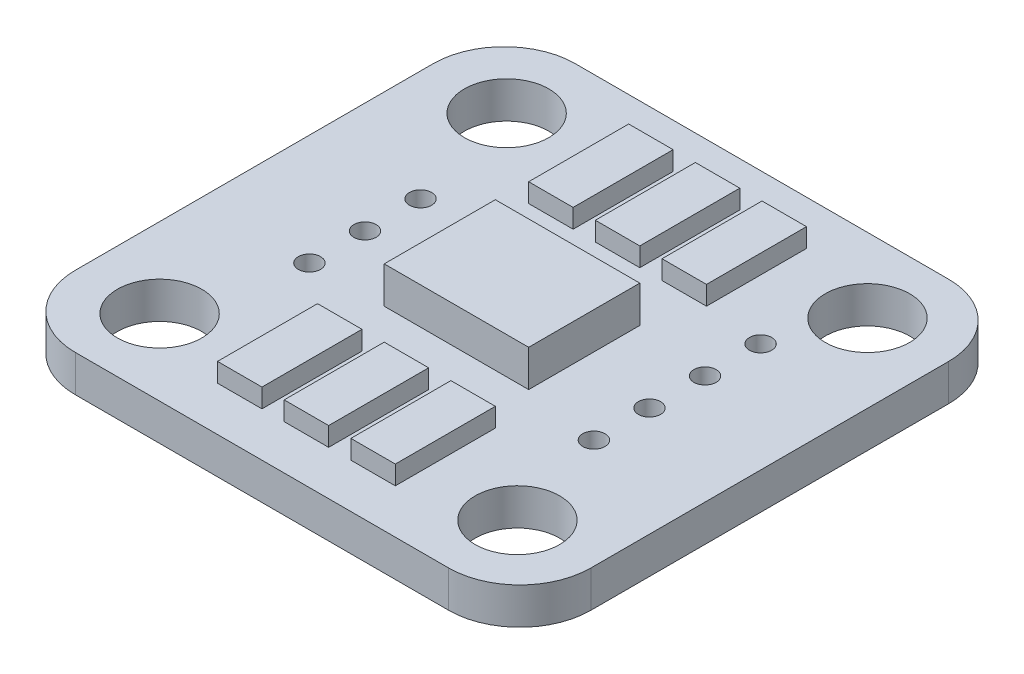
SolidWorks part; units mm, degrees
ref_plane "Front Plane" through (0, 0, 0) normal (0, 0, 1) x (1, 0, 0)
ref_plane "Top Plane" through (0, 0, 0) normal (0, 1, 0) x (1, 0, 0)
ref_plane "Right Plane" through (0, 0, 0) normal (1, 0, 0) x (0, 0, -1)
sketch "Sketch1" plane through (0, 0, 0) normal (0, 1, 0) x (1, 0, 0)
  line L1 (-8.4, -11.25) -> (8.4, -11.25)
  line L2 (-11.6, -8.05) -> (-11.6, 8.05)
  line L3 (-8.4, 11.25) -> (8.4, 11.25)
  line L4 (11.6, -8.05) -> (11.6, 8.05)
  line L5 (-11.6, -11.25) -> (11.6, 11.25) construction
  line L6 (-11.6, 11.25) -> (11.6, -11.25) construction
  line L7 (-8.0152, -7.8409) -> (8.0848, -7.8409) construction
  line L8 (-8.0152, -7.8409) -> (-8.0152, 7.7733) construction
  line L10 (8.0848, -7.8409) -> (8.0848, 7.9091) construction
  line L11 (-8.0152, -7.8409) -> (8.0848, 7.9091) construction
  line L12 (-8.0152, 7.7733) -> (8.0848, -7.8409) construction
  circle A0 centre (-8.0152, 7.7733) radius 1.9
  circle A1 centre (8.0848, 7.9091) radius 1.9
  circle A2 centre (8.0848, -7.8409) radius 1.9
  circle A3 centre (-8.0152, -7.8409) radius 1.9
  arc A4 (-8.4, -11.25) -> (-11.6, -8.05) centre (-8.4, -8.05) cw
  arc A5 (8.4, -11.25) -> (11.6, -8.05) centre (8.4, -8.05) ccw
  arc A6 (8.4, 11.25) -> (11.6, 8.05) centre (8.4, 8.05) cw
  arc A7 (-11.6, 8.05) -> (-8.4, 11.25) centre (-8.4, 8.05) cw
  point P0 (0, 0)
  point P6 (0, 0)
  point P14 (8.4, -8.05)
  point P15 (0, 0)
  point P16 (0, 0)
  dimension "D5" = 3.8
  dimension "D6" = 3.2
  dimension "D1" = 23.2
  dimension "D2" = 22.5
  dimension "D3" = 15.75
  dimension "D4" = 16.1
extrude "Boss-Extrude1" add sketch "Sketch1" along normal blind 1.65
sketch "Sketch3" plane through (0, 1.65, 0) normal (0, 1, 0) x (1, 0, 0)
  line L0 (0, 11.25) -> (0, -11.25) construction
  line L1 (8.4, 11.25) -> (-8.4, 11.25) construction
  line L2 (-8.4, -11.25) -> (8.4, -11.25) construction
  line L3 (2, 4.75) -> (4, 4.75)
  line L4 (-1, 4.75) -> (1, 4.75)
  line L5 (-1, 4.75) -> (-1, 9.25)
  line L6 (-1, 9.25) -> (1, 9.25)
  line L7 (1, 4.75) -> (1, 9.25)
  line L8 (-1, 4.75) -> (1, 9.25) construction
  line L9 (-1, 9.25) -> (1, 4.75) construction
  line L10 (2, 4.75) -> (2, 9.25)
  line L11 (2, 9.25) -> (4, 9.25)
  line L12 (4, 4.75) -> (4, 9.25)
  line L13 (2, 4.75) -> (4, 9.25) construction
  line L14 (2, 9.25) -> (4, 4.75) construction
  line L15 (-2, 9.25) -> (-4, 4.75) construction
  line L16 (-2, 4.75) -> (-4, 9.25) construction
  line L17 (-4, 4.75) -> (-4, 9.25)
  line L18 (-2, 9.25) -> (-4, 9.25)
  line L19 (-2, 4.75) -> (-2, 9.25)
  line L20 (-2, 4.75) -> (-4, 4.75)
  line L21 (-11.6, 0) -> (11.6, 0) construction
  line L22 (-11.6, 8.05) -> (-11.6, -8.05) construction
  line L23 (11.6, -8.05) -> (11.6, 8.05) construction
  line L24 (-2, -4.75) -> (-4, -9.25) construction
  line L25 (-2, -9.25) -> (-4, -4.75) construction
  line L26 (2, -9.25) -> (4, -4.75) construction
  line L27 (2, -4.75) -> (4, -9.25) construction
  line L28 (-1, -9.25) -> (1, -4.75) construction
  line L29 (-1, -4.75) -> (1, -9.25) construction
  line L30 (-2, -4.75) -> (-4, -4.75)
  line L31 (-2, -4.75) -> (-2, -9.25)
  line L32 (-2, -9.25) -> (-4, -9.25)
  line L33 (-4, -4.75) -> (-4, -9.25)
  line L34 (4, -4.75) -> (4, -9.25)
  line L35 (2, -9.25) -> (4, -9.25)
  line L36 (2, -4.75) -> (2, -9.25)
  line L37 (1, -4.75) -> (1, -9.25)
  line L38 (-1, -9.25) -> (1, -9.25)
  line L39 (-1, -4.75) -> (-1, -9.25)
  line L40 (-1, -4.75) -> (1, -4.75)
  line L41 (2, -4.75) -> (4, -4.75)
  point P6 (0, 7)
  point P11 (3, 7)
  point P20 (-3, 7)
  point P39 (-3, -7)
  point P40 (3, -7)
  point P41 (0, -7)
  dimension "D1" = 2
  dimension "D2" = 4.5
  dimension "D3" = 2
  dimension "D5" = 6
  dimension "D4" = 2
extrude "Boss-Extrude2" add sketch "Sketch3" along normal offset from surface (0.85 mm away) 2.5 contours L20 L19 L18 L17 | L4 L7 L6 L5 | L3 L12 L11 L10 | L41 L36 L35 L34 | L40 L39 L38 L37 | L30 L33 L32 L31 region at (3, 1.65, -7) region at (0, 1.65, -7) region at (-3, 1.65, -7) region at (-3, 1.65, 7) region at (3, 1.65, 7) region at (0, 1.65, 7) up to face at (8.0848, 0, 9.7409)
sketch "Sketch4" plane through (0, 1.65, 0) normal (0, 1, 0) x (1, 0, 0)
  line L1 (-3.25, -2.5) -> (3.25, -2.5)
  line L2 (-3.25, -2.5) -> (-3.25, 2.5)
  line L3 (-3.25, 2.5) -> (3.25, 2.5)
  line L4 (3.25, -2.5) -> (3.25, 2.5)
  line L5 (-3.25, -2.5) -> (3.25, 2.5) construction
  line L6 (-3.25, 2.5) -> (3.25, -2.5) construction
  point P0 (0, 0)
  dimension "D1" = 6.5
  dimension "D2" = 5
extrude "Boss-Extrude3" add sketch "Sketch4" along normal offset from surface (1.65 mm away) 3.3 up to face at (8.0848, 0, 9.7409)
sketch "Sketch5" plane through (0, 1.65, 0) normal (0, 1, 0) x (1, 0, 0)
  line L0 (6.6848, 4.5) -> (6.6848, 2) construction
  line L1 (6.6848, 2) -> (6.6848, -0.5) construction
  line L2 (6.6848, -0.5) -> (6.6848, -3) construction
  line L3 (-6.6152, 2.5) -> (-6.6152, 0) construction
  line L4 (-6.6152, 0) -> (-6.6152, -2.5) construction
  line L5 (6.6848, 2.5) -> (3.25, 2.5) construction
  line L6 (-6.1152, 7.7733) -> (-6.1152, -7.8409) construction
  line L7 (6.1848, 7.9091) -> (6.1848, -7.8409) construction
  line L8 (8.4, 11.25) -> (-8.4, 11.25) construction
  circle A0 centre (-6.6152, 0) radius 0.5
  circle A1 centre (-6.6152, 2.5) radius 0.5
  circle A2 centre (-6.6152, -2.5) radius 0.5
  circle A3 centre (6.6848, 4.5) radius 0.5
  circle A4 centre (6.6848, 2) radius 0.5
  circle A5 centre (6.6848, -0.5) radius 0.5
  circle A6 centre (6.6848, -3) radius 0.5
  circle A7 centre (-8.0152, 7.7733) radius 1.9 construction
  circle A8 centre (-8.0152, -7.8409) radius 1.9 construction
  circle A9 centre (8.0848, 7.9091) radius 1.9 construction
  circle A10 centre (8.0848, -7.8409) radius 1.9 construction
  dimension "D2" = 1
  dimension "D1" = 2.5
extrude "Cut-Extrude1" cut sketch "Sketch5" against normal through all
